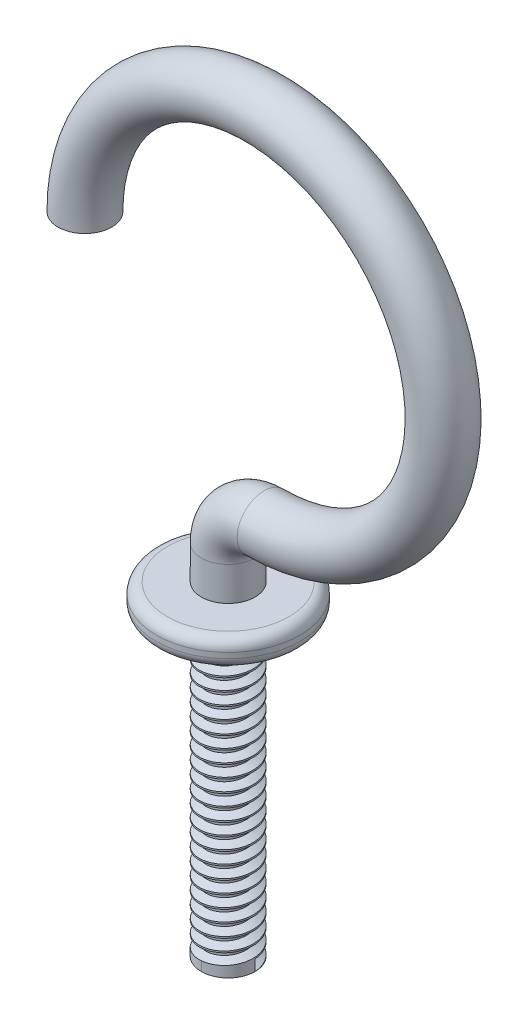
SolidWorks part; units mm, degrees
material "Aço carbono simples"
ref_plane "Plano frontal" through (0, 0, 0) normal (0, 0, 1) x (1, 0, 0)
ref_plane "Plano superior" through (0, 0, 0) normal (0, 1, 0) x (1, 0, 0)
ref_plane "Plano direito" through (0, 0, 0) normal (1, 0, 0) x (0, 0, -1)
sketch "Esboço1" plane through (0, 0, 0) normal (0, 0, 1) x (1, 0, 0)
  line L0 (0, 0) -> (0, 10)
  arc A0 (0, 10) -> (1, 11) centre (1, 10) cw
  arc A1 (1, 11) -> (-4, 16) centre (1, 16) ccw
  dimension "D2" = 5
  dimension "D3" = 1
  dimension "D1" = 16
sweep "Varredura1" add path "Esboço1" circular profile diameter 1.5 parameters "D3"=1.5
thread "Rosca1" pitch 0.35 method cut profile "Perfil da rosca1" start angle 0, offset 0, length 8, pitch 0.35, diameter 1.5
ref_plane "Plano1" through (0.75, 0, 0) normal (0, 0, 1) x (1, 0, 0)
sketch "Perfil da rosca1" plane through (0.75, 0, 0) normal (0, 0, 1) x (1, 0, 0)
  line L0 (0, 0) -> (0, 0.35) construction
  line L11 (0, 0) -> (0, 0.3062)
  line L12 (0, 0.3062) -> (-0.1894, 0.1969)
  line L13 (-0.1894, 0.1969) -> (-0.1894, 0.1094)
  line L15 (-0.1894, 0.1094) -> (0, 0)
  line L17 (-0.1894, 0.1531) -> (0, 0.1531) construction
  point P2 (0, 0)
  dimension "Pitch" = 0.35
  dimension "Profile_Angle" = 60
  dimension "Profile_Land" = 0.0875
  dimension "Profile_Height" = 0.1894
sketch "Esboço2" plane through (0, 0, 0) normal (0, 1, 0) x (1, 0, 0)
  circle A0 centre (0, 0) radius 2
  dimension "D1" = 4
extrude "Ressalto-extrusão1" add sketch "Esboço2" along normal blind 0.75 from vertex separate body starting at point (0.4676, 8.3058, 0.5864)
fillet "Filete1" radius 0.3 2 edges at (0, 9.0558, 2) (0, 8.3058, 2)
